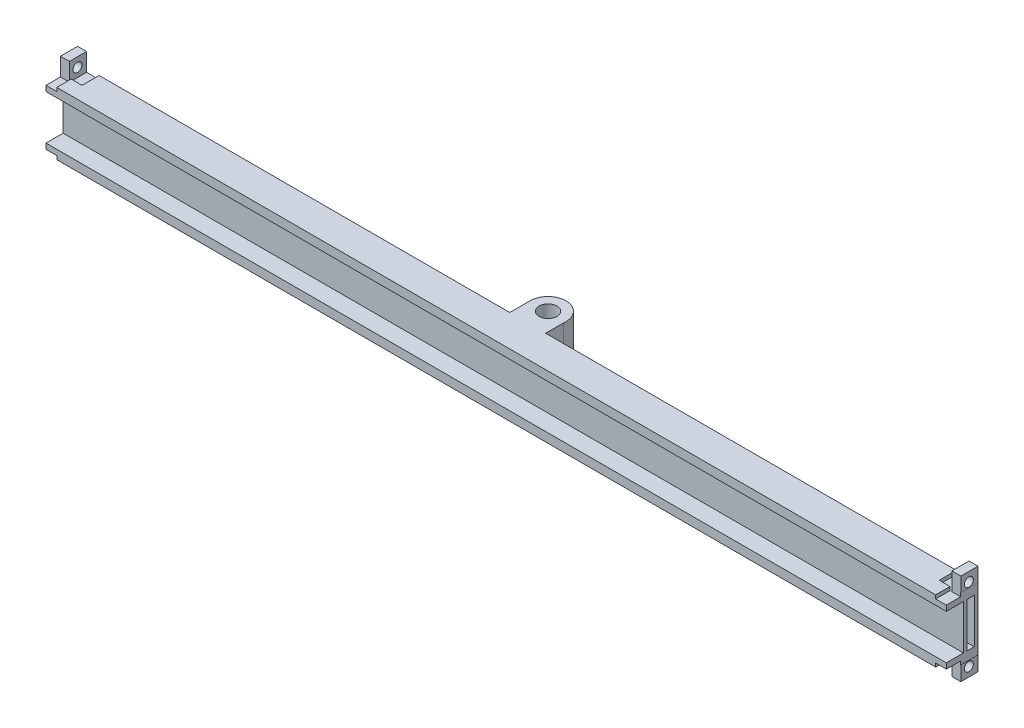
SolidWorks part; units mm, degrees
material "PLA"
ref_plane "Front Plane" through (0, 0, 0) normal (1, 0, 0) x (0, 1, 0)
ref_plane "Top Plane" through (0, 0, 0) normal (0, 0, 1) x (0, 1, 0)
ref_plane "Right Plane" through (0, 0, 0) normal (0, 1, 0) x (-1, 0, 0)
sketch "Sketch1" plane through (0, 0, 0) normal (1, 0, 0) x (0, 1, 0)
  line L16 (0, 4.7625) -> (-2.5, 4.7625)
  line L17 (0, 0) -> (12.3825, 0)
  line L18 (0, 0) -> (0, 4.7625)
  line L19 (0, 4.7625) -> (12.3825, 4.7625) construction
  line L20 (12.3825, 0) -> (12.3825, 4.7625)
  line L21 (-2.5, 4.7625) -> (-2.5, -4)
  line L22 (-2.5, -4) -> (14.8825, -4)
  line L23 (14.8825, -4) -> (14.8825, 4.7625)
  line L24 (12.3825, 4.7625) -> (14.8825, 4.7625)
  dimension "D1" = 4.7625
  dimension "D2" = 12.3825
  dimension "D3" = 2.5
extrude "Boss-Extrude1" add sketch "Sketch1" along normal blind 250
sketch "Sketch3" plane through (0, -2.5, 0) normal (0, -1, 0) x (1, 0, 0)
  line L0 (120.0194, -4) -> (129.9806, -4)
  line L1 (250, -4) -> (0, -4) construction
  line L2 (129.9806, -4) -> (129.9806, -9)
  line L3 (120.0194, -4) -> (120.0194, -9.6217)
  line L4 (0, 4.7625) -> (0, -4) construction
  arc A0 (120.0194, -9.6217) -> (129.9806, -9) centre (125.0194, -9.6217) ccw
  circle A1 centre (125.0194, -9.6217) radius 2.5
  point P5 (125, -4)
  dimension "D3" = 5
  dimension "D4" = 125
extrude "Boss-Extrude2" add sketch "Sketch3" against normal up to surface (17.3825 mm away) up to face at (125, 14.8825, 0.3813)
sketch "Sketch6" plane through (0, -2.5, 0) normal (0, -1, 0) x (1, 0, 0)
  line L0 (120.0194, -4) -> (0, -4) construction
  line L1 (117.5385, -4) -> (131.3691, -4)
  line L2 (117.5385, -4) -> (117.5385, -13.6365)
  line L3 (117.5385, -13.6365) -> (131.3691, -13.6365)
  line L4 (131.3691, -4) -> (131.3691, -13.6365)
extrude "Cut-Extrude2" [suppressed] cut sketch "Sketch6" against normal blind 5
sketch "Sketch7" plane through (0, 14.8825, 0) normal (0, 1, 0) x (-1, 0, 0)
  line L0 (-250, -4) -> (-129.9806, -4) construction
  line L1 (-136.5723, -4) -> (-116.3235, -4)
  line L2 (-136.5723, -4) -> (-136.5723, -14.7915)
  line L3 (-136.5723, -14.7915) -> (-116.3235, -14.7915)
  line L4 (-116.3235, -4) -> (-116.3235, -14.7915)
extrude "Cut-Extrude3" [suppressed] cut sketch "Sketch7" against normal blind 5
sketch "Sketch8" plane through (250, 0, 0) normal (1, 0, 0) x (0, 1, 0)
  line L0 (6.1913, 0) -> (6.1913, -4) construction
  line L5 (12.3825, 0) -> (0, 0) construction
  line L6 (14.8825, -4) -> (-2.5, -4) construction
  line L11 (0, -3) -> (12.3825, -3)
  line L12 (0, -3) -> (0, -1)
  line L13 (0, -1) -> (12.3825, -1)
  line L14 (12.3825, -3) -> (12.3825, -1)
  line L15 (0, -3) -> (12.3825, -1) construction
  line L16 (0, -1) -> (12.3825, -3) construction
  point P6 (6.1913, -2)
  dimension "D1" = 12.3825
extrude "Cut-Extrude4" cut sketch "Sketch8" against normal through all
sketch "Sketch9" plane through (0, 0, -4) normal (0, 0, -1) x (-1, 0, 0)
  line L0 (-117.5194, -2.5) -> (-117.5194, 14.8825) construction
  line L1 (-120.0194, -2.5) -> (0, -2.5) construction
  line L2 (-120.0194, 14.8825) -> (0, 14.8825) construction
  line L3 (-120.0194, 14.8825) -> (-120.0194, -2.5) construction
  line L4 (-116.5194, 12.3825) -> (-118.5194, 12.3825)
  line L5 (-116.5194, 12.3825) -> (-116.5194, 0)
  line L6 (-116.5194, 0) -> (-118.5194, 0)
  line L7 (-118.5194, 12.3825) -> (-118.5194, 0)
  line L8 (-116.5194, 12.3825) -> (-118.5194, 0) construction
  line L9 (-116.5194, 0) -> (-118.5194, 12.3825) construction
  point P6 (-117.5194, 6.1913)
  dimension "D3" = 2.5
  dimension "D1" = 12.3825
extrude "Cut-Extrude5" cut sketch "Sketch9" against normal up to next
ref_plane "Plane1" through (125.0194, 0, 0) normal (-1, 0, 0) x (0, 0, 1)
mirror "Mirror1" about plane through (125.0194, 0, 0) normal (-1, 0, 0) of "Cut-Extrude5"
sketch "Sketch10" plane through (0, 0, 4.7625) normal (0, 0, 1) x (1, 0, 0)
  line L1 (0, 14.8825) -> (2.5, 14.8825)
  line L2 (0, 14.8825) -> (0, 18.8912)
  line L3 (0, 18.8912) -> (2.5, 18.8912)
  line L4 (2.5, 14.8825) -> (2.5, 18.8912)
  line L5 (0, -2.5) -> (2.5, -2.5)
  line L6 (0, -2.5) -> (0, -6.5088)
  line L7 (0, -6.5088) -> (2.5, -6.5088)
  line L8 (2.5, -2.5) -> (2.5, -6.5088)
  dimension "D2" = 25.4
extrude "Boss-Extrude3" add sketch "Sketch10" against normal up to surface (8.7625 mm away) up to face at (117.5194, 6.1913, -4)
mirror "Mirror2" about plane through (125.0194, 0, 0) normal (-1, 0, 0) of "Boss-Extrude3"
sketch "Sketch11" plane through (250.0388, 0, 0) normal (1, 0, 0) x (0, 1, 0)
  circle A0 centre (16.3512, -1.46) radius 1.25 construction
  circle A1 centre (-3.9687, -1.46) radius 1.25 construction
  circle A2 centre (16.3512, -1.46) radius 1.25
  circle A3 centre (-3.9687, -1.46) radius 1.25
extrude "Cut-Extrude6" cut sketch "Sketch11" against normal up to surface (2.5 mm away) up to face at (247.5388, 16.8869, 0.3813)
mirror "Mirror3" about plane through (125.0194, 0, 0) normal (-1, 0, 0) of "Cut-Extrude6"
sketch "Sketch14" plane through (0, 0, 4.7625) normal (0, 0, 1) x (1, 0, 0)
  line L0 (0, 6.1912) -> (17.1619, 6.1912) construction
  line L1 (0, -6.5088) -> (3, -6.5088)
  line L2 (0, -6.5088) -> (0, -1.5088)
  line L3 (0, -1.5088) -> (3, -1.5088)
  line L4 (3, -6.5088) -> (3, -1.5088)
  line L5 (0, 12.3825) -> (0, 0) construction
  line L6 (0, 13.8912) -> (3, 13.8912)
  line L7 (3, 18.8912) -> (3, 13.8912)
  line L8 (0, 18.8912) -> (3, 18.8912)
  line L9 (0, 18.8912) -> (0, 13.8912)
  dimension "D2" = 3
extrude "Cut-Extrude7" cut sketch "Sketch14" against normal blind 4
mirror "Mirror4" about plane through (125.0194, 0, 0) normal (-1, 0, 0) of "Cut-Extrude7"
sketch "Sketch15" plane through (0, -2.5, 0) normal (0, -1, 0) x (-1, 0, 0)
  line L0 (-3, -0.7625) -> (-2.5, -0.7625) construction
  line L1 (-2.5, 4) -> (-6, 4)
  line L2 (-2.5, 4) -> (-2.5, -0.7625)
  line L3 (-2.5, -0.7625) -> (-6, -0.7625)
  line L4 (-6, 4) -> (-6, -0.7625)
  line L5 (0, 4) -> (0, -0.7625) construction
  dimension "D1" = 6
extrude "Cut-Extrude9" cut sketch "Sketch15" against normal blind 1 contours L4 L3 L2 L1
ref_plane "Plane3" through (0, 6.1913, 0) normal (0, 1, 0) x (1, 0, 0)
mirror "Mirror7" about plane through (0, 6.1913, 0) normal (0, 1, 0) of "Cut-Extrude9"
mirror "Mirror8" about plane through (125.0194, 0, 0) normal (-1, 0, 0) of "Mirror7"
equation "\"D1@Sketch1\"=\"ball_diameter\" * 0.25"
equation "\"D2@Sketch1\"=\"ball_diameter\" * 0.65"
equation "\"D3@Sketch1\"=\"wall_thickness\""
equation "\"D4@Sketch1\"=0.4cm"
equation "\"D1@Boss-Extrude1\"=\"track_length\""
equation "\"D2@Sketch3\"= \"axle\""
equation "\"ball_diameter\"= 0.75in"
equation "\"wall_thickness\" = 0.25cm"
equation "\"track_length\" = 25cm"
equation "\"axle\" = 5mm"
equation "\"D3@Sketch3\"=\"axle\" * 1"
equation "\"D4@Sketch3\"=\"track_length\" / 2"
equation "\"pillar_width\" = 2.75cm"
equation "\"D1@Sketch9\"=\"ball_diameter\" * 0.65"
equation "\"D1@Sketch8\"=\"ball_diameter\"*0.65"
equation "\"D1@Sketch10\"=\"wall_thickness\""
equation "\"D2@Sketch14\"=0.3"
